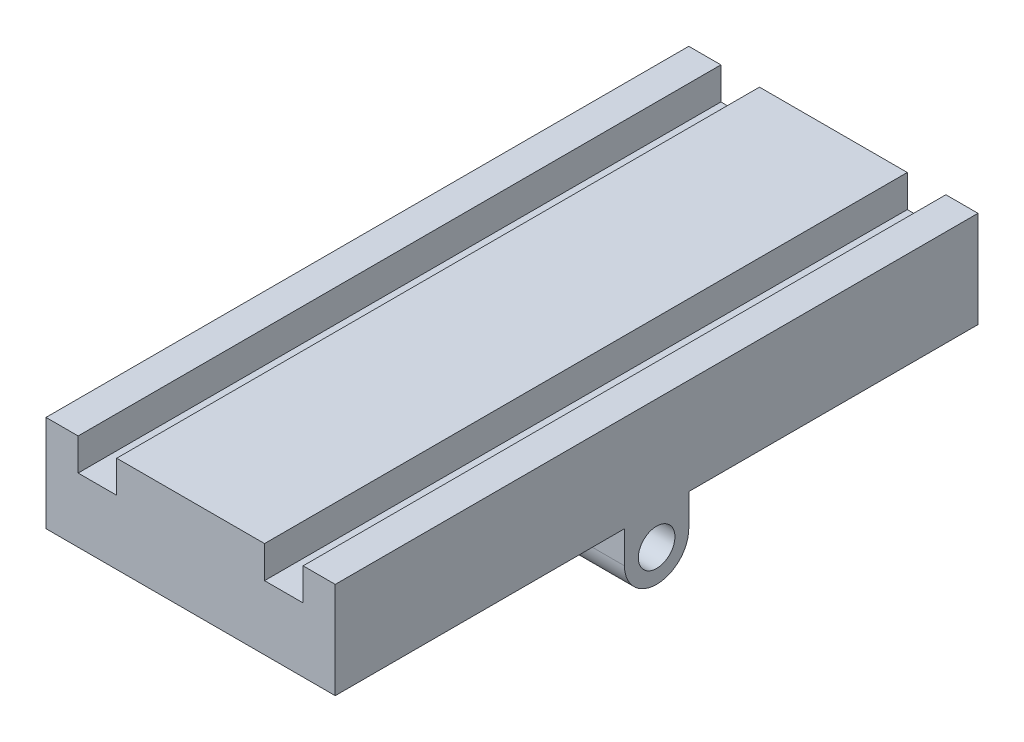
SolidWorks part; units mm, degrees
ref_plane "Front Plane" through (0, 0, 0) normal (0, 0, 1) x (1, 0, 0)
ref_plane "Top Plane" through (0, 0, 0) normal (0, 1, 0) x (1, 0, 0)
ref_plane "Right Plane" through (0, 0, 0) normal (1, 0, 0) x (0, 0, -1)
sketch "Sketch1" plane through (0, 0, 0) normal (0, 0, 1) x (1, 0, 0)
  line L0 (-11.5, 5) -> (11.5, 5)
  line L1 (-11.5, 5) -> (-11.5, 0)
  line L2 (11.5, 5) -> (11.5, 0)
  line L3 (11.5, 0) -> (17.5, 0)
  line L4 (-11.5, 0) -> (-17.5, 0)
  line L5 (-17.5, 0) -> (-17.5, 5)
  line L6 (-17.5, 5) -> (-22.5, 5)
  line L7 (-22.5, 5) -> (-22.5, -10)
  line L8 (-22.5, -10) -> (22.5, -10)
  line L9 (22.5, -10) -> (22.5, 5)
  line L10 (22.5, 5) -> (17.5, 5)
  line L11 (17.5, 5) -> (17.5, 0)
  point P2 (0, 5)
  point P14 (22.5, -13.2199)
  dimension "D1" = 23
  dimension "D2" = 5
  dimension "D3" = 6
  dimension "D4" = 15
  dimension "D5" = 45
extrude "Boss-Extrude1" add sketch "Sketch1" along normal blind 100
sketch "Sketch2" plane through (-22.5, 0, 0) normal (-1, 0, 0) x (0, 0, 1)
  line L0 (100, -10) -> (0, -10) construction
  line L1 (45, -15) -> (45, -10)
  line L2 (55, -15) -> (55, -10)
  line L3 (45, -10) -> (55, -10)
  line L4 (45, -15) -> (55, -15)
  point P0 (50, -15)
  point P4 (50, -10)
  dimension "D1" = 5
  dimension "D2" = 10
extrude "Boss-Extrude3" add sketch "Sketch2" against normal blind 45
sketch "Sketch3" plane through (-22.5, 0, 0) normal (-1, 0, 0) x (0, 0, 1)
  line L0 (45, -15) -> (55, -15) construction
  circle A0 centre (50, -15) radius 5
  circle A1 centre (50, -15) radius 2.85
  dimension "D1" = 5.7
extrude "Boss-Extrude4" add sketch "Sketch3" against normal blind 45 contours A0
sketch "Sketch4" plane through (-22.5, 0, 0) normal (-1, 0, 0) x (0, 0, 1)
  circle A0 centre (50, -15) radius 2.85
  arc A1 (45, -15) -> (55, -15) centre (50, -15) ccw construction
  point P2 (0, 0)
  point P7 (50, -20)
  dimension "D1" = 5.7
extrude "Cut-Extrude1" cut sketch "Sketch4" against normal blind 45
